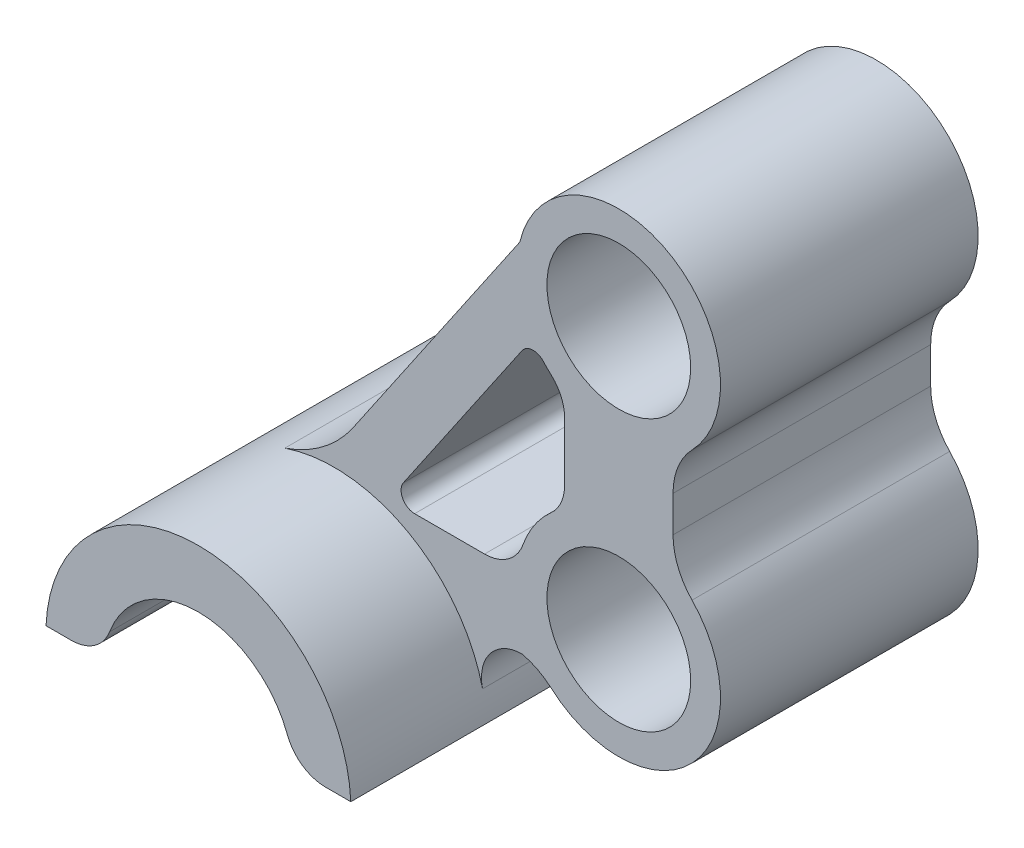
SolidWorks part; units mm, degrees
ref_plane "正面" through (0, 0, 0) normal (0, 0, 1) x (1, 0, 0)
ref_plane "平面" through (0, 0, 0) normal (0, 1, 0) x (1, 0, 0)
ref_plane "右側面" through (0, 0, 0) normal (1, 0, 0) x (0, 0, -1)
sketch "ｽｹｯﾁ1" plane through (0, 0, 0) normal (0, 0, 1) x (1, 0, 0)
  line L1 (4, 14.7) -> (-4, 14.7)
  line L2 (4, 14.7) -> (4, 5.3)
  line L3 (4, 5.3) -> (-4, 5.3)
  line L4 (-4, 14.7) -> (-4, 5.3)
  circle A0 centre (0, 20) radius 5.3
  circle A1 centre (0, 0) radius 5.3
  circle A2 centre (0, 20) radius 7.5
  circle A3 centre (0, 0) radius 7.5
  point P12 (0, 5.3)
  point P13 (0, 0)
  point P14 (0, 0)
  point P15 (0, 0)
  point P16 (-45.9355, 41.0039)
  point P17 (0, 14.7)
  point P19 (0, 25.0046)
  point P20 (0, 25.0046)
  point P21 (0, 0)
  dimension "D1" = 0
  dimension "a" = 10.6
  dimension "D2" = 10.6
  dimension "D3" = 20
  dimension "D4" = 15
  dimension "D6" = 0
  dimension "D5" = 8
extrude "ﾎﾞｽ - 押し出し1" add sketch "ｽｹｯﾁ1" against normal blind 17 and the other way blind 2 contours L4 A3 L2 L3 A1 | L2 A3 L4 L3 | A3 L2 A2 L4 | L4 A2 L2 L1 | L2 A2 L4 L1 A0 region at (0, 13.7546, 0) region at (2, 14.9041, 0) region at (0, 10, 0) region at (6.3882, 3.5242, 0) region at (0, 6.2454, 0)
sketch "ｽｹｯﾁ3" plane through (0, 0, 2) normal (0, 0, 1) x (1, 0, 0)
  line L1 (-6, 0.5) -> (-21, 0.5)
  line L2 (-6, 0.5) -> (-6, -4.5)
  line L3 (-6, -4.5) -> (-21, -4.5)
  line L4 (-21, 0.5) -> (-21, -4.5)
  arc A1 (-4, 6.3443) -> (4, 6.3443) centre (0, 0) ccw construction
  point P4 (-6, -4.4677)
  point P5 (-6, -4.4507)
  point P6 (0, 0)
  point P8 (0, 0)
  point P12 (0, 0)
  dimension "D1" = 5
  dimension "D2" = 15
  dimension "６" = 6
extrude "ﾎﾞｽ - 押し出し3" add sketch "ｽｹｯﾁ3" against normal blind 19
sketch "ｽｹｯﾁ4" plane through (0, 0, 2) normal (0, 0, 1) x (1, 0, 0)
  line L0 (-21, 0.5) -> (-21, -4.5) construction
  line L1 (-32.25, -10.75) -> (-9.75, -10.75)
  line L2 (-21, -4.5) -> (-6, -4.5) construction
  line L3 (-7.4833, 0.5) -> (-21, 0.5) construction
  line L5 (-9.7611, -10.25) -> (-32.2389, -10.25)
  circle A0 centre (-21, -10.75) radius 7
  circle A1 centre (-21, -10.75) radius 11.25
  point P8 (-21, -10.75)
  line M6 (-21, 0.5) -> (-21, -4.5)
  line M7 (-21, -4.5) -> (-6, -4.5)
  dimension "D1" = 14
  dimension "D2" = 0
  dimension "D3" = 11.25
  dimension "D4" = 11.25
  dimension "D5" = 0.5
extrude "ﾎﾞｽ - 押し出し4" add sketch "ｽｹｯﾁ4" against normal blind 19 separate body contours L1 A1 A0 M7 | A1 L1 A0 M6 region at (-12.8881, -7.2084, 2) region at (-26.7982, -4.631, 2)
sketch "ｽｹｯﾁ5" plane through (0, 0, 2) normal (0, 0, 1) x (1, 0, 0)
  circle A0 centre (-21, -10.75) radius 7
extrude "ｶｯﾄ - 押し出し1" cut sketch "ｽｹｯﾁ5" against normal blind 19
sketch "ｽｹｯﾁ6" plane through (0, 0, 2) normal (0, 0, 1) x (1, 0, 0)
  line L0 (-9.7611, -10.25) -> (-32.2389, -10.25)
  circle A0 centre (-21, -10.75) radius 11.25
  circle A1 centre (-21, -10.75) radius 7
  arc M2 (-21, -3.75) -> (-17.8476, -4.5) centre (-21, -10.75) cw
  line M3 (-17.8476, -4.5) -> (-6, -4.5)
  line M10 (-21, 0.5) -> (-21, -3.75)
extrude "ﾎﾞｽ - 押し出し5" add sketch "ｽｹｯﾁ6" along normal blind 10 and the other way blind 29 contours A1 L0 A0 M3 | A0 M3 M10 M2 | A1 A0 L0 M10 region at (-12.8881, -7.2084, 2) region at (-17.2337, -2.3675, 2) region at (-26.7982, -4.631, 2)
fillet "ﾌｨﾚｯﾄ2" radius 3 1 edges at (-11.6459, -4.5, -7.5)
fillet "ﾌｨﾚｯﾄ3" radius 3 2 edges at (-27.9821, -10.25, -7.5) (-14.0179, -10.25, -7.5)
sketch "ｽｹｯﾁ7" plane through (0, 0, 2) normal (0, 0, 1) x (1, 0, 0)
  line L1 (5.7806, 16.0523) -> (-5.7806, 23.9477) construction
  line L2 (-5.7806, 23.9477) -> (-26.7806, -6.8023)
  line L3 (-26.7806, -6.8023) -> (-15.2194, -14.6977) construction
  line L4 (0, 20) -> (-21, -10.75) construction
  line L5 (-5.7806, 23.9477) -> (0, 20)
  line L6 (0, 20) -> (-21, -10.75)
  line L7 (-21, -10.75) -> (-26.7806, -6.8023)
  line L8 (-2.4774, 21.6919) -> (-23.4774, -9.0581)
  circle A0 centre (0, 20) radius 5.3 construction
  arc A2 (-14.4428, -8.3) -> (-27.5572, -8.3) centre (-21, -10.75) ccw construction
  circle A3 centre (0, 20) radius 7.5
  circle A4 centre (-21, -10.75) radius 11.25
  line M9 (-7.4833, 0.5) -> (-21, 0.5)
  arc M15 (4, 13.6557) -> (-4, 13.6557) centre (0, 20) ccw
  dimension "D1" = 0
  dimension "D2" = 0
  dimension "D3" = 7
  dimension "D4" = 3
extrude "ﾎﾞｽ - 押し出し6" add sketch "ｽｹｯﾁ7" against normal blind 19 contours L8 L2 M15 M9 region at (-13.3341, 9.5219, 2)
fillet "ﾌｨﾚｯﾄ4" radius 3 3 edges at (-7.4833, 0.5, -7.5) (-4, 6.3443, -7.5) (-4, 13.6557, -7.5)
fillet "ﾌｨﾚｯﾄ5" radius 1 2 edges at (-16.9499, 0.5, -7.5) (-6.354, 16.0154, -7.5)
fillet "ﾌｨﾚｯﾄ6" radius 5 3 edges at (-6, -4.5, -7.5) (4, 6.3443, -7.5) (4, 13.6557, -7.5)
fillet "ﾌｨﾚｯﾄ7" radius 10 1 edges at (-21.8138, 0.4705, -7.5)
